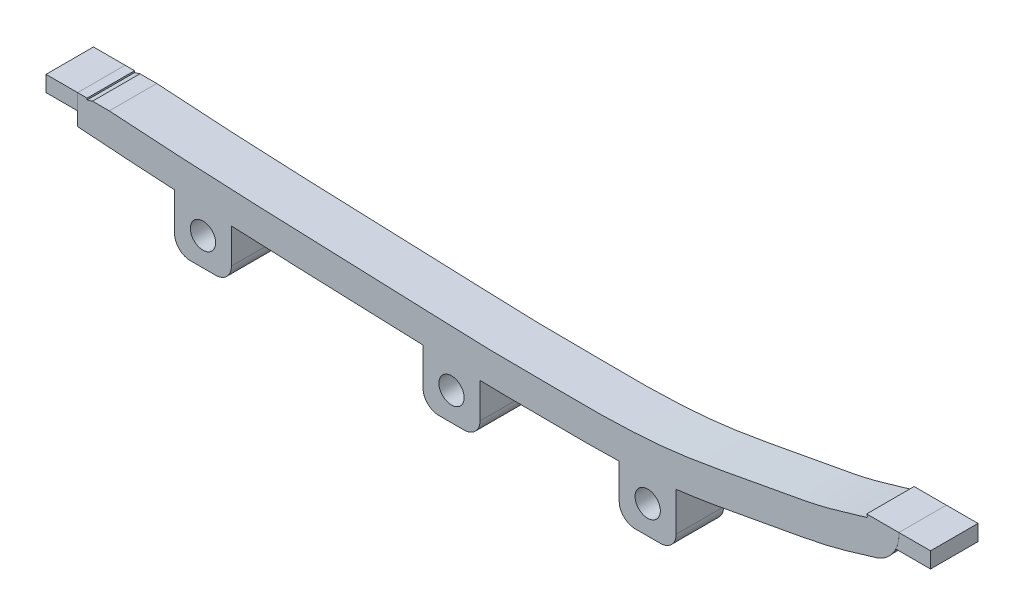
SolidWorks part; units mm, degrees
note: The reader was unsure of these and kept them because the rebuilt part matched: shared geometry of "Sketch10<3>".
ref_plane "Front Plane" through (0, 0, 0) normal (0, 0, 1) x (1, 0, 0)
ref_plane "Top Plane" through (0, 0, 0) normal (0, 1, 0) x (1, 0, 0)
ref_plane "Right Plane" through (0, 0, 0) normal (1, 0, 0) x (0, 0, -1)
sketch "Sketch1" plane through (0, 0, 0) normal (0, 0, 1) x (1, 0, 0)
  line L0 (0, 0) -> (110, 0) construction
  line L1 (110, 0) -> (110, 21) construction
  line L2 (0, 0) -> (110, 21)
  line L3 (23.5, 17.3139) -> (20, 16.6457)
  line L4 (0, 0) -> (20, 0)
  line L5 (20, 0) -> (20, 67.15) construction
  line L6 (0, 0) -> (0, 67.15) construction
  line L7 (0, 67.15) -> (110, 67.15) construction
  line L8 (110, 61.55) -> (110, 67.15)
  line L9 (0, 67.15) -> (110, 61.55)
  line L10 (23.5, 53.9381) -> (81.5, 50.9854)
  line L11 (81.5, 50.9854) -> (81.5, 28.3866)
  line L12 (23.5, 53.9381) -> (23.5, 17.3139)
  line L13 (23.5, 17.3139) -> (81.5, 28.3866)
  line L14 (110, 21) -> (110, 61.55) construction
  line L15 (112, 61.4482) -> (112, 21.3818)
  line L16 (110, 61.55) -> (112, 61.4482)
  line L17 (110, 21) -> (112, 21.3818)
  line L18 (10.9, 67.15) -> (10.9, 0)
  line L19 (0, 67.15) -> (-82.3902, 71.3444)
  line L20 (0, 0) -> (-182.0672, -34.7583)
  line L21 (-86.7, -36.2944) -> (-86.7, -57.7944)
  line L22 (-93.05, 89.1409) -> (-93.05, -40.6456)
  line L23 (-70.5516, 60.184) -> (7.4462, 55.0566)
  line L24 (-89.4413, 54.3923) -> (-89.4413, 37.6042)
  line L25 (-65.3332, 22.0194) -> (-42.2468, 20.2821) construction
  line L26 (-42.2468, 20.2821) -> (-21.4079, 14.5616) construction
  line L27 (-21.4079, 14.5616) -> (-8.5368, 8.8411) construction
  line L28 (-8.5368, 8.8411) -> (-2.8162, 7.0023) construction
  line L29 (-2.8162, 7.0023) -> (0, 0) construction
  line L30 (-235.9653, 18.0968) -> (-234.0715, 53.1142)
  line L31 (-238.05, 59.4719) -> (-238.05, 21) construction
  line L32 (-921.7383, -124.7627) -> (144.2786, -161.9889) construction
  line L34 (-226.3459, 60.184) -> (-104.3294, 60.184)
  line L35 (-82.0567, 37.6042) -> (-82.7237, 57.9466)
  line L36 (-82.3902, 71.3444) -> (-103.6, 72.4242)
  line L37 (-103.6, 72.4242) -> (-103.6, 67.1242)
  line L38 (-103.6, 67.1242) -> (-117.6, 67.1242)
  line L39 (-117.6, 67.1242) -> (-117.6, 72.6011)
  line L40 (-117.6, 72.6011) -> (-158.5, 72.6011)
  line L41 (-158.5, 72.6011) -> (-158.5, 68.6011)
  line L42 (-158.5, 68.6011) -> (-173.5, 69.3647)
  line L43 (-173.5, 69.3647) -> (-173.5, 73.3311)
  line L44 (-173.5, 73.3311) -> (-250.6778, 73.3311)
  line L45 (-250.6778, 73.3311) -> (-251.1351, 64.35)
  line L46 (-251.1351, 64.35) -> (-249.1426, 59.4719)
  line L47 (-249.1426, 59.4719) -> (-253.0614, 11.9612)
  spline_without_curve S0
  spline S1 degree 3 poles (-62.7428, 33.1676) (-50.008, 31.9642) (-31.0962, 32.5015) (-14.1751, 24.9914) (-9.6822, 22.192) knots 0 0 0 0 0.709755 1 1 1 1
  spline S2 degree 3 poles (-9.6822, 22.192) (-6.8917, 20.9668) (-4.0654, 23.2801) (1.077, 24.0309) (6.7349, 23.1276) (13.0796, 25.9871) (10.9, 30.3114) knots 0 0 0 0 0.304362 0.391412 0.603771 1 1 1 1
  spline S3 degree 3 poles (-65.3332, 22.0194) (-77.4805, 22.6509) (-98.8967, 23.1079) (-139.7694, 19.7032) (-187.7649, 10.9991) (-227.3069, 7.5749) (-246.6861, 2.6333) knots 0 0 0 0 0.199692 0.351003 0.672194 1 1 1 1
  spline S4 degree 3 poles (-62.7428, 33.1676) (-67.9368, 33.6388) (-74.1452, 31.6619) (-82.8627, 34.4448) (-82.0567, 37.6042) knots 0 0 0 0 0.65977 1 1 1 1
  spline S5 degree 3 poles (-104.3294, 60.184) (-100.5301, 59.5513) (-93.8007, 61.9485) (-88.7866, 56.5953) (-89.4413, 54.3923) knots 0 0 0 0 0.661964 1 1 1 1
  spline S6 degree 3 poles (-104.3294, 33.547) (-100.6826, 33.3941) (-97.3824, 32.6768) (-91.1309, 33.381) (-89.6784, 34.473) (-89.4413, 37.6042) knots 0 0 0 0 0.555991 0.846219 1 1 1 1
  spline S7 degree 3 poles (-104.3294, 33.547) (-116.4931, 34.3961) (-139.9294, 30.8214) (-169.9623, 27.1478) (-193.8607, 26.9431) (-204.0402, 24.0023) (-211.1217, 23.2564) (-214.8026, 19.376) (-215.2918, 15.9456) (-214.9447, 14.6164) (-218.1891, 14.6988) (-221.7312, 14.9192) (-230.6867, 16.3937) (-236.4685, 15.9971) (-235.9653, 18.0968) knots 0 0 0 0 0.241116 0.431915 0.666521 0.747659 0.783153 0.799752 0.821748 0.858269 0.866885 0.907914 0.932706 1 1 1 1
  spline S8 degree 3 poles (-82.7237, 57.9466) (-82.8248, 63.2577) (-71.0235, 59.3637) (-70.5516, 60.184) knots 0 0 0 0 1 1 1 1
  spline S9 degree 2 poles (7.4462, 55.0566) (12.5645, 55.8042) (10.9, 50.909) knots 0 0 0 1 1 1
  spline S10 degree 3 poles (-234.0715, 53.1142) (-234.3359, 55.4474) (-232.0516, 60.1047) (-228.0459, 60.2249) (-226.3459, 60.184) knots 0 0 0 0 0.618254 1 1 1 1
  spline S11 degree 2 poles (-253.0614, 11.9612) (-252.6953, 7.068) (-247.464, 8.0018) knots 0 0 0 1 1 1
  spline S12 degree 3 poles (-246.6861, 2.6333) (-248.9283, 3.1544) (-247.5659, 6.6016) (-247.464, 8.0018) knots 0 0 0 0 1 1 1 1
  point P55 (-93.05, 46.4253)
  dimension "D1" = 110
  dimension "D2" = 21
  dimension "D3" = 12.6
  dimension "D4" = 20
  dimension "D5" = 67.15
  dimension "D6" = 5.6
  dimension "D7" = 110
  dimension "D8" = 12
  dimension "D9" = 3.5
  dimension "D10" = 58
  dimension "D11" = 2
  dimension "D12" = 12.6
  dimension "D13" = 97.6
  dimension "D14" = 6.35
  dimension "D15" = 14
  dimension "D16" = 145
  dimension "D17" = 15
  dimension "D18" = 40.9
  dimension "D19" = 10.55
  dimension "D20" = 5.3
  dimension "D21" = 4
sketch "Sketch2" plane through (0, 0, 0) normal (0, 0, 1) x (1, 0, 0)
  line L0 (0, 0) -> (110, 21) construction
  line L1 (0, 0) -> (110, 21)
  line L2 (112, 61.4482) -> (112, 21.3818) construction
  line L3 (112, 61.4482) -> (112, 21.3818)
  line L4 (-70.5516, 60.184) -> (7.4462, 55.0566) construction
  line L5 (110, 21) -> (112, 21.3818) construction
  line L6 (110, 21) -> (112, 21.3818)
  line L7 (110, 61.55) -> (112, 61.4482) construction
  line L8 (110, 61.55) -> (112, 61.4482)
  line L9 (0, 67.15) -> (110, 61.55) construction
  line L10 (0, 67.15) -> (110, 61.55)
  line L11 (0, 67.15) -> (-82.3902, 71.3444) construction
  line L12 (0, 67.15) -> (-82.3902, 71.3444)
  line L13 (-82.3902, 71.3444) -> (-103.6, 72.4242) construction
  line L14 (-82.3902, 71.3444) -> (-103.6, 72.4242)
  line L15 (-103.6, 72.4242) -> (-103.6, 67.3782)
  line L16 (-103.6, 67.3782) -> (-117.6, 67.3782)
  line L17 (-117.6, 67.3782) -> (-117.6, 72.6011)
  line L18 (-117.6, 72.6011) -> (-158.5, 72.6011)
  line L19 (-158.5, 72.6011) -> (-158.5, 69.3647)
  line L20 (-158.5, 69.3647) -> (-173.5, 69.3647)
  line L21 (-173.5, 69.3647) -> (-173.5, 73.3311)
  line L22 (-173.5, 73.3311) -> (-250.6778, 73.3311) construction
  line L23 (-173.5, 73.3311) -> (-250.6778, 73.3311)
  line L24 (-250.6778, 73.3311) -> (-253.0614, 11.9612)
  line L25 (-89.4413, 54.3923) -> (-89.4413, 37.6042) construction
  line L26 (-226.3459, 60.184) -> (-104.3294, 60.184) construction
  line L27 (-235.9653, 18.0968) -> (-234.0715, 53.1142) construction
  line L28 (-89.4413, 54.3923) -> (-89.4413, 37.6042)
  line L29 (-226.3459, 60.184) -> (-104.3294, 60.184)
  line L30 (-235.9653, 18.0968) -> (-234.0715, 53.1142)
  line L31 (-82.0567, 37.6042) -> (-82.7237, 57.9466) construction
  line L32 (-70.5516, 60.184) -> (7.4462, 55.0566)
  line L33 (-82.0567, 37.6042) -> (-82.7237, 57.9466)
  line L34 (10.9, 50.909) -> (10.9, 30.3114)
  line L35 (81.5, 50.9854) -> (81.5, 28.3866) construction
  line L36 (23.5, 17.3139) -> (81.5, 28.3866) construction
  line L37 (23.5, 53.9381) -> (81.5, 50.9854) construction
  line L38 (23.5, 53.9381) -> (23.5, 17.3139) construction
  line L39 (81.5, 48.1342) -> (81.5, 30.8681)
  line L40 (27.0626, 17.994) -> (79.0626, 27.9213)
  line L41 (26.6525, 53.7776) -> (78.6525, 51.1303)
  line L42 (23.5, 50.7815) -> (23.5, 20.9408)
  line L43 (-158.5, 72.6011) -> (-158.5, 68.6011) construction
  arc A0 (26.6525, 53.7776) -> (23.5, 50.7815) centre (26.5, 50.7815) ccw
  arc A1 (27.0626, 17.994) -> (23.5, 20.9408) centre (26.5, 20.9408) cw
  arc A2 (81.5, 30.8681) -> (79.0626, 27.9213) centre (78.5, 30.8681) cw
  arc A3 (81.5, 48.1342) -> (78.6525, 51.1303) centre (78.5, 48.1342) ccw
  parabola Q0 (-253.0614, 11.9612) -> (-247.464, 8.0018) focus (-250.6889, 9.8561) apex (-251.6748, 8.6753) construction
  parabola Q1 (-253.0614, 11.9612) -> (-247.464, 8.0018) focus (-250.6889, 9.8561) apex (-251.6748, 8.6753)
  parabola Q2 (7.4462, 55.0566) -> (10.9, 50.909) focus (10.2347, 53.865) apex (10.8693, 54.3929) construction
  parabola Q3 (7.4462, 55.0566) -> (10.9, 50.909) focus (10.2347, 53.865) apex (10.8693, 54.3929)
  spline S0 degree 3 poles (1215.9924, 1366.2087) (-1689.2719, -1445.9602) (1160.7038, 1491.2702) (-1612.7605, -1453.4516) knots -5.972872 -5.972872 -5.972872 -5.972872 7.300913 7.300913 7.300913 7.300913 only from (-246.6861, 2.6333) to (-247.464, 8.0018) construction
  spline S1 degree 3 poles (-246.6861, 2.6333) (-248.9283, 3.1544) (-247.5659, 6.6016) (-247.464, 8.0018) knots 0 0 0 0 1 1 1 1
  spline S2 degree 3 poles (175.3636, 1967.872) (391.9741, -245.9956) (130.7811, 42.2402) (-139.7694, 19.7032) (-325.1272, -13.9116) (-514.1452, 28.671) (-309.5796, -1983.4136) knots -3.777296 -3.777296 -3.777296 -3.777296 0.199692 0.351003 0.672194 3.290466 3.290466 3.290466 3.290466 only from (-65.3332, 22.0194) to (-246.6861, 2.6333) construction
  spline S3 degree 3 poles (-65.3332, 22.0194) (-77.4805, 22.6509) (-98.8967, 23.1079) (-139.7694, 19.7032) (-187.7649, 10.9991) (-227.3069, 7.5749) (-246.6861, 2.6333) knots 0 0 0 0 0.199692 0.351003 0.672194 1 1 1 1
  spline S4 degree 5 poles (1876.0426, 360.0904) (-1729.8867, -1179.746) (583.5253, 1803.2982) (78.4446, -2000.9415) (-313.5377, 2017.6127) (349.0217, -1969.1752) knots -2.469726 -2.469726 -2.469726 -2.469726 -2.469726 -2.469726 2.883008 2.883008 2.883008 2.883008 2.883008 2.883008 only from (-65.3332, 22.0194) to (0, 0) construction
  spline S5 degree 5 poles (-65.3332, 22.0194) (-42.2468, 20.2821) (-21.4079, 14.5616) (-8.5368, 8.8411) (-2.8162, 7.0023) (0, 0) knots 0 0 0 0 0 0 1 1 1 1 1 1
  spline S6 degree 3 poles (-2003.4226, -592.8129) (-74.6134, 83.2569) (-127.2178, 29.3158) (-83.3934, 34.2526) (-91.8628, 46.616) (-191.2637, 2034.7775) knots -4.772522 -4.772522 -4.772522 -4.772522 0.555991 0.846219 2.237697 2.237697 2.237697 2.237697 only from (-104.3294, 33.547) to (-89.4413, 37.6042) construction
  spline S7 degree 3 poles (-884.1428, -1800.4231) (147.9483, 84.9453) (-58.8059, 40.7444) (-169.9623, 27.1478) (-193.8607, 26.9431) (-204.0402, 24.0023) (-211.1217, 23.2564) (-214.8026, 19.376) (-215.2918, 15.9456) (-214.9447, 14.6164) (-218.1891, 14.6988) (-221.7312, 14.9192) (-259.045, 21.0628) (-280.7399, -17.3172) (1437.9042, 1112.0112) knots -1.800378 -1.800378 -1.800378 -1.800378 0.241116 0.431915 0.666521 0.747659 0.783153 0.799752 0.821748 0.858269 0.866885 0.907914 0.932706 1.421519 1.421519 1.421519 1.421519 only from (-104.3294, 33.547) to (-235.9653, 18.0968) construction
  spline S8 degree 3 poles (879.86, 1711.5652) (-207.6215, -132.0929) (-295.8251, 232.0271) (-122.4858, -93.2389) (-314.6686, 2056.7417) knots -5.484197 -5.484197 -5.484197 -5.484197 0.618254 6.842445 6.842445 6.842445 6.842445 only from (-234.0715, 53.1142) to (-226.3459, 60.184) construction
  spline S9 degree 3 poles (-104.3294, 33.547) (-100.6826, 33.3941) (-97.3824, 32.6768) (-91.1309, 33.381) (-89.6784, 34.473) (-89.4413, 37.6042) knots 0 0 0 0 0.555991 0.846219 1 1 1 1
  spline S10 degree 3 poles (-104.3294, 33.547) (-116.4931, 34.3961) (-139.9294, 30.8214) (-169.9623, 27.1478) (-193.8607, 26.9431) (-204.0402, 24.0023) (-211.1217, 23.2564) (-214.8026, 19.376) (-215.2918, 15.9456) (-214.9447, 14.6164) (-218.1891, 14.6988) (-221.7312, 14.9192) (-230.6867, 16.3937) (-236.4685, 15.9971) (-235.9653, 18.0968) knots 0 0 0 0 0.241116 0.431915 0.666521 0.747659 0.783153 0.799752 0.821748 0.858269 0.866885 0.907914 0.932706 1 1 1 1
  spline S11 degree 3 poles (-234.0715, 53.1142) (-234.3359, 55.4474) (-232.0516, 60.1047) (-228.0459, 60.2249) (-226.3459, 60.184) knots 0 0 0 0 0.618254 1 1 1 1
  spline S12 degree 3 poles (319.5224, 2014.3086) (-192.9155, -111.4852) (-73.7068, 193.2347) (-74.1309, -42.5933) (-2079.8517, 234.6153) knots -4.398535 -4.398535 -4.398535 -4.398535 0.661964 3.952777 3.952777 3.952777 3.952777 only from (-104.3294, 60.184) to (-89.4413, 54.3923) construction
  spline S13 degree 3 poles (-104.3294, 60.184) (-100.5301, 59.5513) (-93.8007, 61.9485) (-88.7866, 56.5953) (-89.4413, 54.3923) knots 0 0 0 0 0.661964 1 1 1 1
  spline S14 degree 3 poles (-476.921, 1966.6082) (-22.6367, -59.8265) (-22.4132, 20.601) (1.077, 24.0309) (25.1351, 20.1898) (79.5245, 97.6802) (-1928.1805, 515.6228) knots -2.154256 -2.154256 -2.154256 -2.154256 0.304362 0.391412 0.603771 3.262307 3.262307 3.262307 3.262307 only from (-9.6822, 22.192) to (10.9, 30.3114) construction
  spline S15 degree 3 poles (290.3742, 1996.6931) (-276.3479, -157.1226) (45.2421, 284.1781) (112.1059, -304.2564) (-1943.388, -409.2218) knots -4.781032 -4.781032 -4.781032 -4.781032 0.709755 6.530859 6.530859 6.530859 6.530859 only from (-62.7428, 33.1676) to (-9.6822, 22.192) construction
  spline S16 degree 3 poles (1014.7339, -1650.8552) (-65.1434, 157.9827) (-20.1321, -37.6544) (-136.3103, 72.496) (1711.8022, 920.8151) knots -4.712693 -4.712693 -4.712693 -4.712693 0.65977 3.302586 3.302586 3.302586 3.302586 only from (-62.7428, 33.1676) to (-82.0567, 37.6042) construction
  spline S17 degree 3 poles (1566.4817, -1072.7309) (-1852.9005, 1150.0589) (1734.6604, -974.3467) (-1819.0286, 1030.9337) knots -3.685572 -3.685572 -3.685572 -3.685572 4.790703 4.790703 4.790703 4.790703 only from (-82.7237, 57.9466) to (-70.5516, 60.184) construction
  spline S18 degree 3 poles (-9.6822, 22.192) (-6.8917, 20.9668) (-4.0654, 23.2801) (1.077, 24.0309) (6.7349, 23.1276) (13.0796, 25.9871) (10.9, 30.3114) knots 0 0 0 0 0.304362 0.391412 0.603771 1 1 1 1
  spline S19 degree 3 poles (-62.7428, 33.1676) (-50.008, 31.9642) (-31.0962, 32.5015) (-14.1751, 24.9914) (-9.6822, 22.192) knots 0 0 0 0 0.709755 1 1 1 1
  spline S20 degree 3 poles (-62.7428, 33.1676) (-67.9368, 33.6388) (-74.1452, 31.6619) (-82.8627, 34.4448) (-82.0567, 37.6042) knots 0 0 0 0 0.65977 1 1 1 1
  spline S21 degree 3 poles (-82.7237, 57.9466) (-82.8248, 63.2577) (-71.0235, 59.3637) (-70.5516, 60.184) knots 0 0 0 0 1 1 1 1
  point P6 (-2.1894, 23.46)
  dimension "D1" = 3
  dimension "D2" = 3
  dimension "D3" = 14
sketch "Sketch7" plane through (0, 0, -6) normal (0, 0, -1) x (-1, 0, 0)
  line L0 (57.2, -13.2414) -> (57.2, 17.7586)
  line L1 (34.2, -9.2119) -> (34.2, 14.5881)
  line L2 (78.2, 18.0862) -> (78.2, -15.0138)
  line L3 (100.2, 16.9853) -> (100.2, -15.1147)
  line L4 (120.2, 14.7624) -> (120.2, -14.9376)
  line L5 (249.35, -19.0412) -> (249.35, -8.2188)
  line L9 (236.35, 2.8687) -> (236.35, 5.7682)
  line L10 (236.35, 5.7682) -> (244.27, 5.7682)
  line L11 (239.35, -9.7188) -> (239.35, -8.2188)
  line L12 (10.85, 8.1639) -> (10.85, -4.4861)
  line L13 (244.27, 5.7682) -> (244.27, 5.7682)
  line L14 (244.27, 5.7682) -> (244.27, 5.7682)
  line L15 (244.27, 5.7682) -> (244.27, 5.7682)
  line L16 (244.27, 5.7682) -> (244.27, 5.7682)
  line L40 (246.35, -10.2318) -> (246.35, -4.2318)
  line L41 (246.35, -4.2318) -> (249.35, -4.2318)
  line L42 (249.35, -4.2318) -> (249.35, -10.4223)
  line L43 (249.35, -10.4223) -> (261.435, -8.6139)
  line L44 (261.435, -8.6139) -> (261.435, -0.35)
  line L45 (261.435, -0.35) -> (254.27, -1.2771)
  line L46 (254.27, -1.2771) -> (254.27, 49.29)
  line L47 (254.27, 49.29) -> (264.27, 48.7037)
  line L48 (264.27, 48.7037) -> (264.27, 57.5188)
  line L49 (264.27, 57.5188) -> (249.35, 58.3935)
  line L50 (249.35, 58.3935) -> (249.35, 52.5694)
  line L51 (249.35, 52.5694) -> (246.35, 52.5694)
  line L52 (246.35, 52.5694) -> (246.35, 58.5694)
  line L53 (246.35, 58.5694) -> (174.35, 62.7905)
  line L54 (174.35, 62.7905) -> (174.35, 57.7819)
  line L55 (174.35, 57.7819) -> (159.35, 58.6614)
  line L56 (159.35, 58.6614) -> (159.35, 63.6699)
  line L57 (159.35, 63.6699) -> (118.45, 66.0678)
  line L58 (118.45, 66.0678) -> (118.45, 61.5601)
  line L59 (118.45, 61.5601) -> (104.45, 62.3808)
  line L60 (104.45, 62.3808) -> (104.45, 66.8886)
  line L61 (104.45, 66.8886) -> (89.45, 67.768)
  line L62 (89.45, 67.768) -> (89.45, 62.3703)
  line L63 (89.45, 62.3703) -> (86.45, 62.3703)
  line L64 (86.45, 62.3703) -> (86.45, 68.0433)
  line L65 (86.45, 68.0433) -> (-16.3334, 66.995)
  line L66 (-16.3334, 66.995) -> (-19.25, 66.904)
  line L67 (-19.25, 66.904) -> (-19.25, 60.904)
  line L68 (-19.25, 60.904) -> (-22.25, 60.904)
  line L69 (-22.25, 60.904) -> (-22.25, 66.8105)
  line L70 (-22.25, 66.8105) -> (-121.5262, 63.715)
  line L71 (-121.5262, 63.715) -> (-121.5262, 25.4812)
  line L72 (-121.5262, 25.4812) -> (-22.25, 4.3794)
  line L73 (-22.25, 4.3794) -> (-22.25, 9.7417)
  line L74 (-22.25, 9.7417) -> (-19.25, 9.7417)
  line L75 (-19.25, 9.7417) -> (-19.25, 3.7417)
  line L76 (-19.25, 3.7417) -> (0, -0.35)
  line L77 (86.45, 17.816) -> (86.45, 24.6703)
  line L78 (86.45, 24.6703) -> (89.45, 24.6703)
  line L79 (89.45, 24.6703) -> (89.45, 17.676)
  line L80 (246.35, -10.2318) -> (246.35, -4.2318)
  line L81 (246.35, -4.2318) -> (249.35, -4.2318)
  line L82 (249.35, -4.2318) -> (249.35, -10.4223)
  line L83 (249.35, -10.4223) -> (261.435, -8.6139)
  line L84 (261.435, -8.6139) -> (261.435, -0.35)
  line L85 (261.435, -0.35) -> (254.27, -1.2771)
  line L116 (-9.8605, 1.7459) -> (0, -0.35)
  line L117 (86.45, 17.816) -> (86.45, 24.6703)
  line L118 (86.45, 24.6703) -> (89.45, 24.6703)
  line L119 (89.45, 24.6703) -> (89.45, 17.676)
  line L128 (-9.25, 11.8396) -> (-4.1474, 10.755) construction
  line L129 (-9.25, 19.7417) -> (-9.25, 11.8396) construction
  line L130 (-32.25, 19.7417) -> (-9.25, 19.7417) construction
  line L131 (-32.25, 16.7284) -> (-32.25, 19.7417) construction
  line L132 (-111.5262, 33.579) -> (-32.25, 16.7284) construction
  line L134 (-19.25, 3.7417) -> (0, -0.35) construction
  line L135 (-19.25, 9.7417) -> (-19.25, 3.7417) construction
  line L136 (-22.25, 4.3794) -> (-22.25, 9.7417) construction
  line L137 (-22.25, 9.7417) -> (-19.25, 9.7417) construction
  line L138 (-121.5262, 25.4812) -> (-22.25, 4.3794) construction
  line L139 (76.45, 28.1254) -> (76.45, 34.6703) construction
  line L140 (76.45, 34.6703) -> (99.45, 34.6703) construction
  line L141 (99.45, 34.6703) -> (99.45, 27.0734) construction
  line L142 (-9.25, 50.904) -> (-32.25, 50.904) construction
  line L143 (-16.3334, 66.995) -> (-19.25, 66.904) construction
  line L144 (-19.25, 66.904) -> (-19.25, 60.904) construction
  line L145 (-19.25, 60.904) -> (-22.25, 60.904) construction
  line L146 (-22.25, 60.904) -> (-22.25, 66.8105) construction
  line L147 (-22.25, 66.8105) -> (-121.5262, 63.715) construction
  line L148 (-121.5262, 63.715) -> (-121.5262, 25.4812) construction
  line L149 (-32.25, 50.904) -> (-32.25, 56.4938) construction
  line L150 (-32.25, 56.4938) -> (-111.5262, 54.0219) construction
  line L151 (-111.5262, 54.0219) -> (-111.5262, 33.579) construction
  line L152 (244.27, 42.5694) -> (244.27, 42.5694) construction
  line L153 (244.27, 42.5694) -> (244.27, 42.5694) construction
  line L154 (244.27, 42.5694) -> (244.27, 42.5694) construction
  line L155 (244.27, 42.5694) -> (244.27, 42.5694) construction
  line L156 (244.27, 42.5694) -> (236.35, 42.5694) construction
  line L157 (236.35, 42.5694) -> (236.35, 49.1385) construction
  line L158 (236.35, 49.1385) -> (184.35, 52.1871) construction
  line L159 (184.35, 52.1871) -> (184.35, 47.1785) construction
  line L160 (184.35, 47.1785) -> (149.35, 49.2305) construction
  line L161 (149.35, 49.2305) -> (149.35, 54.239) construction
  line L162 (149.35, 54.239) -> (128.45, 55.4643) construction
  line L163 (128.45, 55.4643) -> (128.45, 50.9566) construction
  line L164 (128.45, 50.9566) -> (99.45, 52.6568) construction
  line L165 (99.45, 52.6568) -> (99.45, 52.6568) construction
  line L166 (99.45, 52.6568) -> (99.45, 52.6568) construction
  line L167 (99.45, 52.6568) -> (99.45, 52.3703) construction
  line L168 (99.45, 52.3703) -> (76.45, 52.3703) construction
  line L169 (76.45, 52.3703) -> (76.45, 57.9408) construction
  line L170 (254.27, 49.29) -> (264.27, 48.7037) construction
  line L171 (264.27, 48.7037) -> (264.27, 57.5188) construction
  line L172 (264.27, 57.5188) -> (249.35, 58.3935) construction
  line L173 (249.35, 58.3935) -> (249.35, 52.5694) construction
  line L174 (249.35, 52.5694) -> (246.35, 52.5694) construction
  line L175 (246.35, 52.5694) -> (246.35, 58.5694) construction
  line L176 (246.35, 58.5694) -> (174.35, 62.7905) construction
  line L177 (174.35, 62.7905) -> (174.35, 57.7819) construction
  line L178 (174.35, 57.7819) -> (159.35, 58.6614) construction
  line L179 (159.35, 58.6614) -> (159.35, 63.6699) construction
  line L180 (159.35, 63.6699) -> (118.45, 66.0678) construction
  line L181 (118.45, 66.0678) -> (118.45, 61.5601) construction
  line L182 (118.45, 61.5601) -> (104.45, 62.3808) construction
  line L183 (104.45, 62.3808) -> (104.45, 66.8886) construction
  line L184 (104.45, 66.8886) -> (89.45, 67.768) construction
  line L185 (89.45, 67.768) -> (89.45, 62.3703) construction
  line L186 (89.45, 62.3703) -> (86.45, 62.3703) construction
  line L187 (86.45, 62.3703) -> (86.45, 68.0433) construction
  line L188 (244.27, 5.7682) -> (244.27, 42.5694) construction
  line L189 (254.27, -1.2771) -> (254.27, 49.29) construction
  line L190 (76.45, 57.9408) -> (-9.25, 57.0667) construction
  line L191 (-9.25, 57.0667) -> (-9.25, 57.0667) construction
  line L192 (-9.25, 57.0667) -> (-9.25, 50.904) construction
  line L193 (86.45, 68.0433) -> (-16.3334, 66.995) construction
  line L194 (0, -0.35) -> (-10.1882, -0.35)
  line L195 (239.35, -9.7188) -> (249.35, -9.7188)
  line L196 (249.35, -9.7188) -> (249.35, 0.2812)
  arc A0 (99.45, 27.0734) -> (99.45, 27.0734) centre (99.45, 27.0734) cw
  arc A1 (92.0622, 17.5345) -> (89.45, 17.676) centre (70.9391, -348.1742) ccw
  arc A2 (92.0622, 17.5345) -> (89.45, 17.676) centre (70.9391, -348.1742) ccw
  spline S0 degree 5 poles (0, -0.35) (3.1789, 6.4953) (8.9878, 8.0322) (22.1406, 13.0712) (43.2504, 17.6932) (66.396, 18.2199) knots 0 0 0 0 0 0 1 1 1 1 1 1 construction
  spline S1 degree 3 poles (66.396, 18.2199) (73.0799, 18.2171) (79.7689, 18.1017) (86.45, 17.816) knots 0.875946 0.875946 0.875946 0.875946 0.985674 0.985674 0.985674 0.985674 construction
  spline S2 degree 3 poles (92.0622, 17.5345) (95.666, 17.3341) (108.4649, 16.4288) (140.621, 12.1175) (188.0527, 1.0331) (227.3036, -4.3666) (246.35, -10.2318) knots 0 0 0 0 0.059228 0.210539 0.53173 0.858409 0.858409 0.858409 0.858409 construction
  spline S3 degree 3 poles (819.6154, 6883.2001) (-654.3106, -532.7689) (-239.7371, 63.1137) (140.621, 12.1175) (403.2905, -49.2661) (691.7794, 47.5443) (-692.468, -6913.9411) knots -5.757851 -5.757851 -5.757851 -5.757851 0.059228 0.210539 0.53173 4.484966 4.484966 4.484966 4.484966 only from (92.0622, 17.5345) to (246.35, -10.2318)
  spline S4 degree 5 poles (-1413.1581, -6854.4994) (1049.5738, 6970.1281) (-97.6589, -6889.5772) (-1760.7734, 6390.5668) (4440.3702, -5144.3035) (-5995.026, 3243.3569) knots -2.641748 -2.641748 -2.641748 -2.641748 -2.641748 -2.641748 4.262355 4.262355 4.262355 4.262355 4.262355 4.262355 only from (0, -0.35) to (66.396, 18.2199)
  spline S5 degree 3 poles (836.3446, 6890.0394) (-1938.3142, -6910.3307) (1848.5758, 6957.5025) (-340.5582, -6892.2905) knots -4.74365 -4.74365 -4.74365 -4.74365 6.077222 6.077222 6.077222 6.077222 only from (66.396, 18.2199) to (86.45, 17.816)
  spline S6 degree 3 poles (92.0622, 17.5345) (95.666, 17.3341) (108.4649, 16.4288) (140.621, 12.1175) (188.0527, 1.0331) (227.3036, -4.3666) (246.35, -10.2318) knots 0 0 0 0 0.059228 0.210539 0.53173 0.858409 0.858409 0.858409 0.858409
  spline S7 degree 5 poles (0, -0.35) (3.1789, 6.4953) (8.9878, 8.0322) (22.1406, 13.0712) (43.2504, 17.6932) (66.396, 18.2199) knots 0 0 0 0 0 0 1 1 1 1 1 1
  spline S8 degree 3 poles (66.396, 18.2199) (73.0799, 18.2171) (79.7689, 18.1017) (86.45, 17.816) knots 0.875946 0.875946 0.875946 0.875946 0.985674 0.985674 0.985674 0.985674
  spline S9 degree 1 poles (-8.703, 4.5753) (249.35, -19.0412) knots 0 0 1 1 construction
  spline S10 degree 3 poles (0, -0.35) (-0.4835, -1.2043) (1.302, -1.6482) (7.2657, -3.5042) (17.4308, -6.2995) (34.6316, -9.169) (49.5094, -12.1501) (63.8955, -14.1997) (72.042, -14.7877) (85.7541, -15.2977) (99.588, -15.0488) (116.9249, -15.1249) (166.4135, -13.1954) (205.0499, -12.1274) (239.35, -9.7188) knots 0 0 0 0 0.015238 0.061098 0.075476 0.153291 0.229561 0.246275 0.312196 0.329378 0.409853 0.483053 0.542068 1 1 1 1
  spline S11 degree 3 poles (-8.703, 4.5753) (-8.7713, 4.4546) (-8.9, 4.2192) (-9.1743, 3.6747) (-9.4696, 2.9978) (-9.7559, 2.1523) (-9.9387, 1.4558) (-10.0697, 0.7913) (-10.1676, 0.0608) (-10.225, -0.9086) (-10.1514, -2.4353) (-9.676, -4.5233) (-8.5306, -6.7602) (-7.0758, -8.4525) (-5.6792, -9.554) (-4.1346, -10.4423) (-2.8809, -10.8994) (-2.1502, -11.1081) (-1.991, -11.1512) (-1.7433, -11.2216) (-1.3978, -11.3207) (-0.8989, -11.4663) (-0.2236, -11.6659) (0.5197, -11.8872) (1.3192, -12.1262) (2.4483, -12.4636) (3.9542, -12.912) (5.8534, -13.468) (7.7664, -14.0133) (9.7659, -14.5554) (12.6287, -15.2645) (16.3516, -16.0775) (21.025, -16.9906) (25.7806, -17.8596) (30.5055, -18.7016) (35.0354, -19.5303) (39.4929, -20.3676) (45.4015, -21.4656) (51.3449, -22.5015) (57.5236, -23.399) (63.5663, -24.1228) (69.2965, -24.5912) (74.9061, -24.8937) (79.1295, -25.064) (83.3728, -25.1618) (88.8879, -25.2051) (95.6174, -25.1508) (103.4279, -25.0907) (111.417, -25.0835) (119.6665, -24.982) (127.9641, -24.7069) (136.0606, -24.3932) (146.7027, -24.0034) (159.7689, -23.5349) (175.127, -22.9764) (195.2677, -22.1898) (215.0315, -21.27) (232.2271, -20.2383) (242.0493, -19.5549) (246.9124, -19.2124) (249.35, -19.0412) knots 0 0 0 0 0.000508 0.001017 0.002034 0.002658 0.003166 0.003554 0.003942 0.00445 0.005085 0.006102 0.007119 0.008136 0.009153 0.01017 0.012204 0.014238 0.016272 0.018306 0.02034 0.024407 0.028475 0.032543 0.036611 0.040679 0.048815 0.056951 0.065087 0.073222 0.081358 0.09763 0.113902 0.130173 0.146445 0.162716 0.178988 0.19526 0.227803 0.244075 0.260346 0.29289 0.309161 0.325433 0.341705 0.357976 0.390519 0.423063 0.455606 0.488149 0.520693 0.553236 0.585779 0.650866 0.715952 0.781039 0.911212 0.976299 1.008842 1.041385 1.041385 1.041385 1.041385
  spline S12 degree 1 poles (-4.1474, 10.755) (66.2843, 28.22) knots 0 0 1 1 construction
  spline S13 degree 1 poles (66.2843, 28.22) (76.45, 28.1254) knots 0 0 1 1 construction
  spline S14 degree 1 poles (99.45, 27.0734) (236.35, 2.8687) knots 0 0 1 1 construction
  spline S15 degree 3 poles (-4.1474, 10.755) (-3.7466, 11.1356) (-2.9107, 11.8731) (-1.8665, 12.6763) (-1.0206, 13.2717) (-0.137, 13.8595) (1.465, 14.8318) (3.8159, 16.0456) (7.7536, 17.7582) (13.2562, 19.6987) (21.153, 21.9528) (30.4798, 24.1229) (39.4239, 25.7494) (47.2058, 26.831) (53.3247, 27.4991) (58.6312, 27.9068) (62.9776, 28.1259) (65.1846, 28.1949) (66.2843, 28.22) knots 0.135157 0.135157 0.135157 0.135157 0.162215 0.189273 0.201061 0.21459 0.243388 0.297503 0.351618 0.459849 0.568079 0.676309 0.78454 0.838655 0.89277 0.946885 0.973943 1.001001 1.001001 1.001001 1.001001
  spline S16 degree 3 poles (66.2843, 28.22) (67.1295, 28.2196) (68.8186, 28.2159) (71.3603, 28.1987) (73.9032, 28.1695) (75.6013, 28.1416) (76.45, 28.1254) knots 0.875312 0.875312 0.875312 0.875312 0.888961 0.90261 0.91626 0.929909 0.929909 0.929909 0.929909
  spline S17 degree 3 poles (99.45, 27.0734) (105.3352, 26.631) (115.5807, 25.5696) (128.6091, 23.6641) (140.1341, 21.6888) (153.0089, 19.2215) (168.538, 16.0152) (182.4779, 13.1721) (193.559, 11.1112) (201.9816, 9.6377) (210.4866, 8.155) (219.0636, 6.5917) (227.6815, 4.8749) (233.475, 3.5684) (236.35, 2.8687) knots 0.036389 0.036389 0.036389 0.036389 0.130372 0.200031 0.247022 0.318338 0.412321 0.506304 0.553296 0.600287 0.647279 0.694271 0.741262 0.788254 0.788254 0.788254 0.788254
  spline S18 degree 2 poles (-8.703, 4.5753) (-5.858, 10.1325) (-0.7174, 13.4724) knots 0 0 0 1 1 1
  spline S19 degree 2 poles (76.45, 28.1254) (105.5819, 27.71) (134.3179, 22.6791) knots 0 0 0 1 1 1
  spline S21 degree 1 poles (236.35, 2.8687) (249.35, 0.2812) knots 0 0 1 1
  dimension "D2" = 34.2
  dimension "D3" = 23.8
  dimension "D4" = 23
  dimension "D5" = 31
  dimension "D6" = 21
  dimension "D7" = 33.1
  dimension "D8" = 22
  dimension "D9" = 32.1
  dimension "D10" = 29.7
  dimension "D11" = 20
  dimension "D12" = 1.5
  dimension "D13" = 7
  dimension "D14" = 12.65
  dimension "D15" = 10.85
  dimension "D16" = 10
  dimension "D18" = 10
  dimension "D1" = 0
  dimension "D17" = 10
extrude "Boss-Extrude4" add sketch "Sketch7" along normal blind 15 separate body contours L194 S11 L5 L195 L80 S6 S10
sketch "Sketch9" plane through (0, 0, -6) normal (0, 0, 1) x (1, 0, 0)
  line L0 (10.1882, -0.35) -> (20.1882, -0.35)
  line L5 (20.1882, -0.35) -> (20.1882, -5.35)
  line L6 (20.1882, -5.35) -> (9.2198, -5.35)
  line L7 (9.2198, -5.35) -> (-66.678, -5.35)
  line L10 (-249.8068, -9.7188) -> (-249.35, -9.7188)
  line L11 (-249.35, -9.5092) -> (-249.35, -9.7188)
  line L15 (-249.35, -14.7188) -> (-249.35, -9.7188)
  line L16 (-249.35, -9.7188) -> (-259.35, -9.7188)
  line L17 (-249.35, -9.7188) -> (-249.35, -14.7188)
  line L18 (-249.35, -14.7188) -> (-259.35, -14.7188)
  line L19 (-259.35, -9.7188) -> (-259.35, -14.7188)
  line L20 (-66.678, -5.35) -> (-66.678, -24.4847)
  spline S0 degree 3 poles (8.703, 4.5753) (8.7713, 4.4546) (8.9, 4.2192) (9.1743, 3.6747) (9.4696, 2.9978) (9.7559, 2.1523) (9.9387, 1.4558) (10.0697, 0.7913) (10.1676, 0.0608) (10.225, -0.9086) (10.1514, -2.4353) (9.676, -4.5233) (8.5306, -6.7602) (7.0758, -8.4525) (5.6792, -9.554) (4.1346, -10.4423) (2.8809, -10.8994) (2.1502, -11.1081) (1.991, -11.1512) (1.7433, -11.2216) (1.3978, -11.3207) (0.8989, -11.4663) (0.2236, -11.6659) (-0.5197, -11.8872) (-1.3192, -12.1262) (-2.4483, -12.4636) (-3.9542, -12.912) (-5.8534, -13.468) (-7.7664, -14.0133) (-9.7659, -14.5554) (-12.6287, -15.2645) (-16.3516, -16.0775) (-21.025, -16.9906) (-25.7806, -17.8596) (-30.5055, -18.7016) (-35.0354, -19.5303) (-39.4929, -20.3676) (-45.4015, -21.4656) (-51.3449, -22.5015) (-57.5236, -23.399) (-63.5663, -24.1228) (-69.2965, -24.5912) (-74.9061, -24.8937) (-79.1295, -25.064) (-83.3728, -25.1618) (-88.8879, -25.2051) (-95.6174, -25.1508) (-103.4279, -25.0907) (-111.417, -25.0835) (-119.6665, -24.982) (-127.9641, -24.7069) (-136.0606, -24.3932) (-146.7027, -24.0034) (-159.7689, -23.5349) (-175.127, -22.9764) (-195.2677, -22.1898) (-215.0315, -21.27) (-232.2271, -20.2383) (-242.0493, -19.5549) (-246.9124, -19.2124) (-249.35, -19.0412) knots 0 0 0 0 0.000508 0.001017 0.002034 0.002658 0.003166 0.003554 0.003942 0.00445 0.005085 0.006102 0.007119 0.008136 0.009153 0.01017 0.012204 0.014238 0.016272 0.018306 0.02034 0.024407 0.028475 0.032543 0.036611 0.040679 0.048815 0.056951 0.065087 0.073222 0.081358 0.09763 0.113902 0.130173 0.146445 0.162716 0.178988 0.19526 0.227803 0.244075 0.260346 0.29289 0.309161 0.325433 0.341705 0.357976 0.390519 0.423063 0.455606 0.488149 0.520693 0.553236 0.585779 0.650866 0.715952 0.781039 0.911212 0.976299 1.008842 1.041385 1.041385 1.041385 1.041385 construction
  point P4 (-67.007, -27.4475)
  point P17 (-66.9374, -24.7205)
  point P18 (-66.678, -24.4847)
  line M14 (-249.35, -9.7188) -> (-249.35, -19.0412)
  spline M15 degree 3 poles (-249.35, -19.0412) (-246.9124, -19.2124) (-242.0493, -19.5549) (-232.2271, -20.2383) (-215.0315, -21.27) (-195.2677, -22.1898) (-175.127, -22.9764) (-159.7689, -23.5349) (-146.7027, -24.0034) (-136.0606, -24.3932) (-127.9641, -24.7069) (-119.6665, -24.982) (-111.417, -25.0835) (-103.4279, -25.0907) (-95.6174, -25.1508) (-88.8879, -25.2051) (-83.3728, -25.1618) (-79.1295, -25.064) (-74.9061, -24.8937) (-69.2965, -24.5912) (-63.5663, -24.1228) (-57.5236, -23.399) (-51.3449, -22.5015) (-45.4015, -21.4656) (-39.4929, -20.3676) (-35.0354, -19.5303) (-30.5055, -18.7016) (-25.7806, -17.8596) (-21.025, -16.9906) (-16.3516, -16.0775) (-12.6287, -15.2645) (-9.7659, -14.5554) (-7.7664, -14.0133) (-5.8534, -13.468) (-3.9542, -12.912) (-2.4483, -12.4636) (-1.3192, -12.1262) (-0.5197, -11.8872) (0.2236, -11.6659) (0.8989, -11.4663) (1.3978, -11.3207) (1.7433, -11.2216) (1.991, -11.1512) (2.1502, -11.1081) (2.8809, -10.8994) (4.1346, -10.4423) (5.6792, -9.554) (7.0758, -8.4525) (8.5306, -6.7602) (9.676, -4.5233) (10.1514, -2.4353) (10.225, -0.9086) (10.1676, 0.0608) (10.0697, 0.7913) (9.9387, 1.4558) (9.7559, 2.1523) (9.4696, 2.9978) (9.1743, 3.6747) (8.9, 4.2192) (8.7713, 4.4546) (8.703, 4.5753) knots 0 0 0 0 0.032543 0.065087 0.130173 0.260346 0.325433 0.390519 0.455606 0.488149 0.520693 0.553236 0.585779 0.618322 0.650866 0.683409 0.699681 0.715952 0.732224 0.748496 0.781039 0.797311 0.813582 0.846125 0.862397 0.878669 0.89494 0.911212 0.927484 0.943755 0.960027 0.968163 0.976299 0.984434 0.99257 1.000706 1.004774 1.008842 1.01291 1.016978 1.021046 1.02308 1.025114 1.027147 1.029181 1.031215 1.032232 1.033249 1.034266 1.035283 1.0363 1.036935 1.037444 1.037831 1.038219 1.038727 1.039351 1.040368 1.040877 1.041385 1.041385 1.041385 1.041385 only from (-249.35, -19.0412) to (10.1882, -0.35)
  dimension "D1" = 5
  dimension "D2" = 10
  dimension "D3" = 10
  dimension "D4" = 5
extrude "Boss-Extrude6" add sketch "Sketch9" against normal blind 15 separate body contours L6 L5 L0 M15 | L16 L19 L18 L10 M14
sketch "Sketch10" plane through (0, 0, -6) normal (0, 0, 1) x (1, 0, 0)
  line L0 (-78.2, -15.0138) -> (-78.2, -36.0138)
  line L1 (-73.2, -41.0138) -> (-65.2, -41.0138)
  line L4 (-78.2, -15.0138) -> (-60.2, -15.0138)
  line L5 (-60.2, -15.0138) -> (-60.2, -36.0138)
  line L6 (-69.2, -41.0138) -> (-69.2, -32.1482)
  line L7 (-100.2, 16.9853) -> (-100.2, -15.1147) construction
  line L8 (-100.2, 16.9853) -> (-100.2, -15.1147)
  line L9 (-122.2, -15.0138) -> (-140.2, -15.0138)
  line L10 (-140.2, -15.0138) -> (-140.2, -36.0138)
  line L11 (-127.2, -41.0138) -> (-135.2, -41.0138)
  line L12 (-122.2, -15.0138) -> (-122.2, -36.0138)
  line L13 (-200.7451, -11.9075) -> (-218.7451, -11.9075)
  line L14 (-205.7451, -37.9075) -> (-213.7451, -37.9075)
  line L15 (-200.7451, -11.9075) -> (-200.7451, -32.9075)
  line L16 (-218.7451, -11.9075) -> (-218.7451, -32.9075)
  circle A0 centre (-69.2, -32.1482) radius 4
  arc A1 (-60.2, -36.0138) -> (-65.2, -41.0138) centre (-65.2, -36.0138) cw
  arc A2 (-73.2, -41.0138) -> (-78.2, -36.0138) centre (-73.2, -36.0138) cw
  circle A3 centre (-131.2, -32.1482) radius 4
  arc A4 (-140.2, -36.0138) -> (-135.2, -41.0138) centre (-135.2, -36.0138) ccw
  arc A5 (-127.2, -41.0138) -> (-122.2, -36.0138) centre (-127.2, -36.0138) ccw
  arc A6 (-218.7451, -32.9075) -> (-213.7451, -37.9075) centre (-213.7451, -32.9075) ccw
  arc A7 (-205.7451, -37.9075) -> (-200.7451, -32.9075) centre (-205.7451, -32.9075) ccw
  circle A8 centre (-209.7451, -29.0418) radius 4
  spline M14 degree 3 poles (-249.35, -19.0412) (-246.9124, -19.2124) (-242.0493, -19.5549) (-232.2271, -20.2383) (-215.0315, -21.27) (-195.2677, -22.1898) (-175.127, -22.9764) (-159.7689, -23.5349) (-146.7027, -24.0034) (-136.0606, -24.3932) (-127.9641, -24.7069) (-119.6665, -24.982) (-111.417, -25.0835) (-103.4279, -25.0907) (-95.6174, -25.1508) (-88.8879, -25.2051) (-83.3728, -25.1618) (-79.1295, -25.064) (-74.9061, -24.8937) (-69.2965, -24.5912) (-63.5663, -24.1228) (-57.5236, -23.399) (-51.3449, -22.5015) (-45.4015, -21.4656) (-39.4929, -20.3676) (-35.0354, -19.5303) (-30.5055, -18.7016) (-25.7806, -17.8596) (-21.025, -16.9906) (-16.3516, -16.0775) (-12.6287, -15.2645) (-9.7659, -14.5554) (-7.7664, -14.0133) (-5.8534, -13.468) (-3.9542, -12.912) (-2.4483, -12.4636) (-1.3192, -12.1262) (-0.5197, -11.8872) (0.2236, -11.6659) (0.8989, -11.4663) (1.3978, -11.3207) (1.7433, -11.2216) (1.991, -11.1512) (2.1502, -11.1081) (2.8809, -10.8994) (4.1346, -10.4423) (5.6792, -9.554) (7.0758, -8.4525) (8.5306, -6.7602) (9.676, -4.5233) (10.1514, -2.4353) (10.225, -0.9086) (10.1676, 0.0608) (10.0697, 0.7913) (9.9387, 1.4558) (9.7559, 2.1523) (9.4696, 2.9978) (9.1743, 3.6747) (8.9, 4.2192) (8.7713, 4.4546) (8.703, 4.5753) knots 0 0 0 0 0.032543 0.065087 0.130173 0.260346 0.325433 0.390519 0.455606 0.488149 0.520693 0.553236 0.585779 0.618322 0.650866 0.683409 0.699681 0.715952 0.732224 0.748496 0.781039 0.797311 0.813582 0.846125 0.862397 0.878669 0.89494 0.911212 0.927484 0.943755 0.960027 0.968163 0.976299 0.984434 0.99257 1.000706 1.004774 1.008842 1.01291 1.016978 1.021046 1.02308 1.025114 1.027147 1.029181 1.031215 1.032232 1.033249 1.034266 1.035283 1.0363 1.036935 1.037444 1.037831 1.038219 1.038727 1.039351 1.040368 1.040877 1.041385 1.041385 1.041385 1.041385 only from (-249.35, -19.0412) to (10.1882, -0.35)
  dimension "D3" = 5
  dimension "D4" = 8
  dimension "D1" = 26
  dimension "D2" = 18
extrude "Boss-Extrude7" add sketch "Sketch10" against normal blind 15
extrude "Boss-Extrude8" add sketch "Sketch10<3>" against normal blind 15 contours L14 A7 L15 L16 A6 A8 M14 | L11 A5 L12 L10 A4 A3 M14
sketch "Sketch10<3>" plane through (0, 0, -6) normal (0, 0, 1) x (1, 0, 0) same geometry as "Sketch10"
